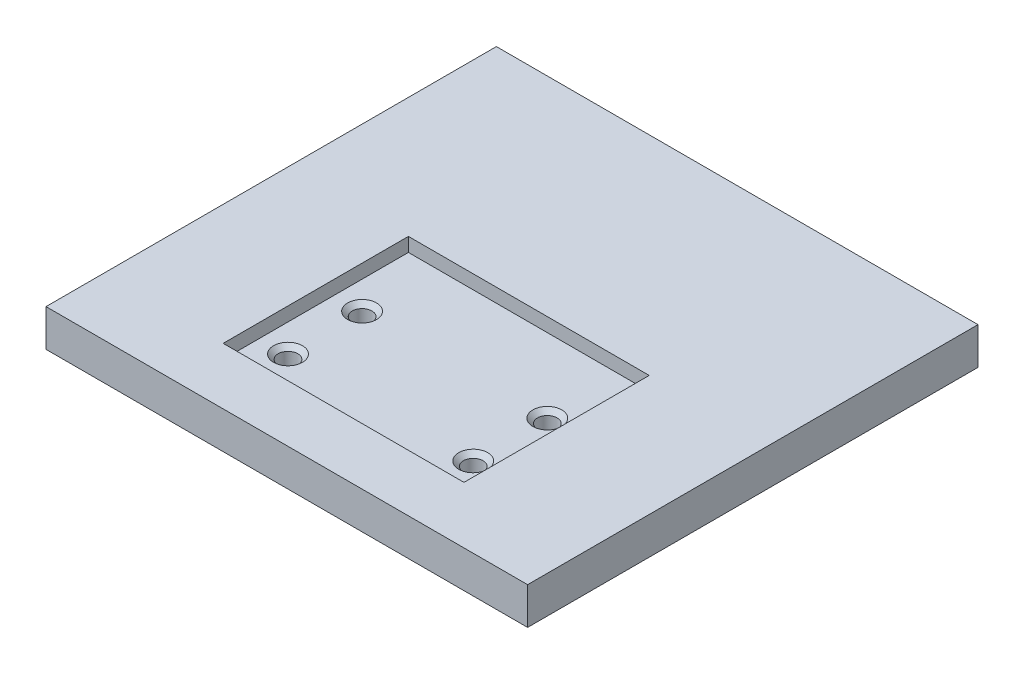
SolidWorks part; units mm, degrees
ref_plane "Front Plane" through (0, 0, 0) normal (0, 0, 1) x (1, 0, 0)
ref_plane "Top Plane" through (0, 0, 0) normal (0, 1, 0) x (1, 0, 0)
ref_plane "Right Plane" through (0, 0, 0) normal (1, 0, 0) x (0, 0, -1)
sketch "Sketch1" plane through (0, 0, 0) normal (0, 1, 0) x (1, 0, 0)
  line L0 (0, 0) -> (0, 46.1982) construction
  line L2 (26, 20) -> (-26, 20)
  line L3 (-26, 20) -> (-26, -20)
  line L4 (-26, -20) -> (26, -20)
  line L5 (26, 20) -> (26, -20)
  circle A0 centre (-20, 4) radius 2.12
  circle A1 centre (-20, 4) radius 2.75
  circle A2 centre (20, 4) radius 2.12
  circle A3 centre (20, 4) radius 2.75
  circle A4 centre (-20, -12) radius 2.12
  circle A5 centre (-20, -12) radius 2.75
  circle A6 centre (20, -12) radius 2.12
  circle A7 centre (20, -12) radius 2.75
  point P5 (-20, 4)
  point P6 (-20, -12)
  point P22 (0, 20)
  point P26 (0, 20)
  dimension "D2" = 0.63
  dimension "D7" = 6
  dimension "D1" = 16
  dimension "D3" = 26
  dimension "D5" = 6
  dimension "D6" = 16
  dimension "D8" = 8
extrude "Boss-Extrude10" add sketch "Sketch1" along normal blind 5 contours L5 L2 L3 L4 A5 A1 A3 A7 region at (0, 0, -0.1915)
extrude "Boss-Extrude13" add sketch "Sketch1<21>" along normal blind 5 contours A3
sketch "Sketch1<21>" plane through (0, 0, 0) normal (0, 1, 0) x (1, 0, 0) same geometry as "Sketch1"
extrude "Cut-Extrude4" cut sketch "Sketch1<22>" along normal blind 7 contours A2
sketch "Sketch1<22>" plane through (0, 0, 0) normal (0, 1, 0) x (1, 0, 0) same geometry as "Sketch1"
chamfer "Chamfer1" distance 1 angle 45 1 edges at (20, 5, -1.88)
extrude "Boss-Extrude14" add sketch "Sketch1<23>" along normal blind 5 contours A7
sketch "Sketch1<23>" plane through (0, 0, 0) normal (0, 1, 0) x (1, 0, 0) same geometry as "Sketch1"
extrude "Cut-Extrude6" cut sketch "Sketch1<24>" along normal blind 5 contours A6
sketch "Sketch1<24>" plane through (0, 0, 0) normal (0, 1, 0) x (1, 0, 0) same geometry as "Sketch1"
extrude "Boss-Extrude15" add sketch "Sketch1<25>" along normal blind 5 contours A5
sketch "Sketch1<25>" plane through (0, 0, 0) normal (0, 1, 0) x (1, 0, 0) same geometry as "Sketch1"
extrude "Cut-Extrude7" cut sketch "Sketch1<26>" along normal blind 18 contours A4
sketch "Sketch1<26>" plane through (0, 0, 0) normal (0, 1, 0) x (1, 0, 0) same geometry as "Sketch1"
extrude "Boss-Extrude17" add sketch "Sketch1<29>" along normal blind 5 contours A1
sketch "Sketch1<29>" plane through (0, 0, 0) normal (0, 1, 0) x (1, 0, 0) same geometry as "Sketch1"
extrude "Cut-Extrude9" cut sketch "Sketch1<30>" along normal blind 14 contours A0
sketch "Sketch1<30>" plane through (0, 0, 0) normal (0, 1, 0) x (1, 0, 0) same geometry as "Sketch1"
chamfer "Chamfer3" distance 1 angle 45 1 edges at (-20, 5, -1.88)
chamfer "Chamfer4" distance 1 angle 45 1 edges at (-20, 5, 14.12)
chamfer "Chamfer5" distance 1 angle 45 1 edges at (20, 5, 9.88)
sketch "Sketch5" plane through (0, 0, 0) normal (0, 1, 0) x (1, 0, 0)
  line L0 (52, 20) -> (-52, 20)
  line L3 (0, -70) -> (0, 57.3138) construction
  line L5 (-26, 20) -> (-26, -20)
  line L6 (-26, -20) -> (26, -20)
  line L7 (26, -20) -> (26, 20)
  line L8 (-52, 20) -> (-52, 65)
  line L9 (-52, 20) -> (-52, -32.2581)
  line L10 (-52, -32.2581) -> (52, -32.2581)
  line L11 (-52, 65) -> (52, 65)
  line L12 (52, 20) -> (52, -32.2581)
  line L13 (52, 20) -> (52, 65)
  point P9 (0, 20)
  point P20 (0, -32.2581)
  point P21 (0, 65)
  dimension "D1" = 52
extrude "Boss-Extrude19" add sketch "Sketch5" along normal blind 8 contours L0 L13 L11 L8 | L10 L3 L6 L5 L0 L9 | L3 L10 L12 L0 L7 L6 region at (34.06, 0, 9.9291) region at (39, 0, -21.1332) region at (-34.06, 0, 9.9291)
